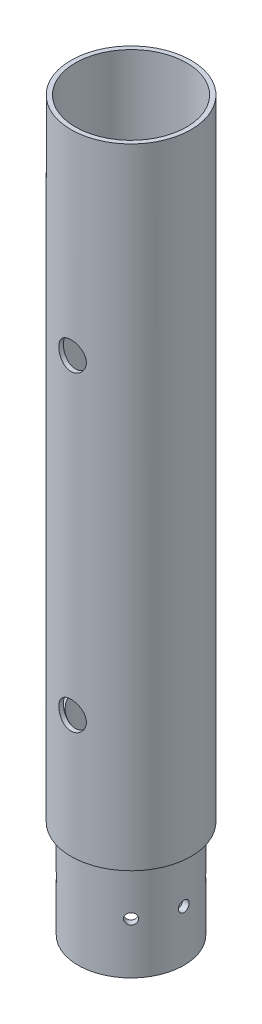
SolidWorks part; units mm, degrees
ref_plane "前视基准面" through (0, 0, 0) normal (0, 0, 1) x (1, 0, 0)
ref_plane "上视基准面" through (0, 0, 0) normal (0, 1, 0) x (1, 0, 0)
ref_plane "右视基准面" through (0, 0, 0) normal (1, 0, 0) x (0, 0, -1)
sketch "草图1" plane through (0, 0, 0) normal (0, 1, 0) x (1, 0, 0)
  circle A0 centre (0, 0) radius 125
  circle A1 centre (0, 0) radius 135
  dimension "D1" = 270
  dimension "D2" = 250
extrude "凸台-拉伸1" add sketch "草图1" along normal blind 1195
sketch "草图10" plane through (0, 0, 0) normal (0, -1, 0) x (-1, 0, 0)
  circle A0 centre (0, 0) radius 105
  circle A1 centre (0, 0) radius 135
  dimension "D1" = 270
  dimension "D2" = 210
extrude "凸台-拉伸2" add sketch "草图10" along normal blind 220
sketch "草图11" plane through (0, -220, 0) normal (0, -1, 0) x (1, 0, 0)
  circle A0 centre (0, 0) radius 105
  circle A1 centre (0, 0) radius 119
  circle A2 centre (0, 0) radius 105 construction
  dimension "D1" = 238
extrude "凸台-拉伸3" add sketch "草图11" along normal blind 220
ref_axis "基准轴1" through (0, 1276.75, 0) along (0, -1, 0)
ref_plane "基准面1" through (0, 0, 500) normal (0, 0, 1) x (1, 0, 0)
ref_plane "基准面7" through (-250, 0, 250) normal (0.7071, 0, -0.7071) x (-0.7071, 0, -0.7071)
ref_plane "基准面8" through (250, 0, 250) normal (0.7071, 0, 0.7071) x (0.7071, 0, -0.7071)
ref_plane "基准面10" through (500, 0, 0) normal (1, 0, 0) x (0, 0, -1)
sketch "草图4" plane through (0, 0, 500) normal (0, 0, 1) x (1, 0, 0)
  line L0 (0, 1124) -> (0, 51124) construction
  line L1 (125, 1195) -> (-125, 1195) construction
  circle A0 centre (0, 755) radius 31
  circle A1 centre (0, 55) radius 31
  point P5 (0, 1195)
  dimension "D1" = 62
  dimension "D2" = 440
  dimension "D3" = 700
extrude "切除-拉伸1" cut sketch "草图4" against normal through all
sketch "草图7" plane through (-250, 0, 250) normal (0.7071, 0, -0.7071) x (-0.7071, 0, -0.7071)
  line L0 (0, -1000) -> (0, 49000) construction
  line L1 (-119, -440) -> (119, -440) construction
  circle A0 centre (0, -325) radius 12
  dimension "D1" = 24
  dimension "D2" = 115
extrude "切除-拉伸3" cut sketch "草图7" along normal through all
sketch "草图8" plane through (250, 0, 250) normal (0.7071, 0, 0.7071) x (0.7071, 0, -0.7071)
  line L0 (0, -1000) -> (0, 49000) construction
  line L1 (-119, -440) -> (119, -440) construction
  circle A0 centre (0, -325) radius 12
  dimension "D2" = 24
  dimension "D1" = 115
extrude "切除-拉伸4" cut sketch "草图8" against normal through all
sketch "草图9" plane through (500, 0, 0) normal (1, 0, 0) x (0, 0, -1)
  line L0 (0, -1000) -> (0, 49000) construction
  line L1 (-119, -440) -> (119, -440) construction
  circle A0 centre (0, -325) radius 12
  dimension "D2" = 24
  dimension "D1" = 115
extrude "切除-拉伸5" cut sketch "草图9" against normal through all
